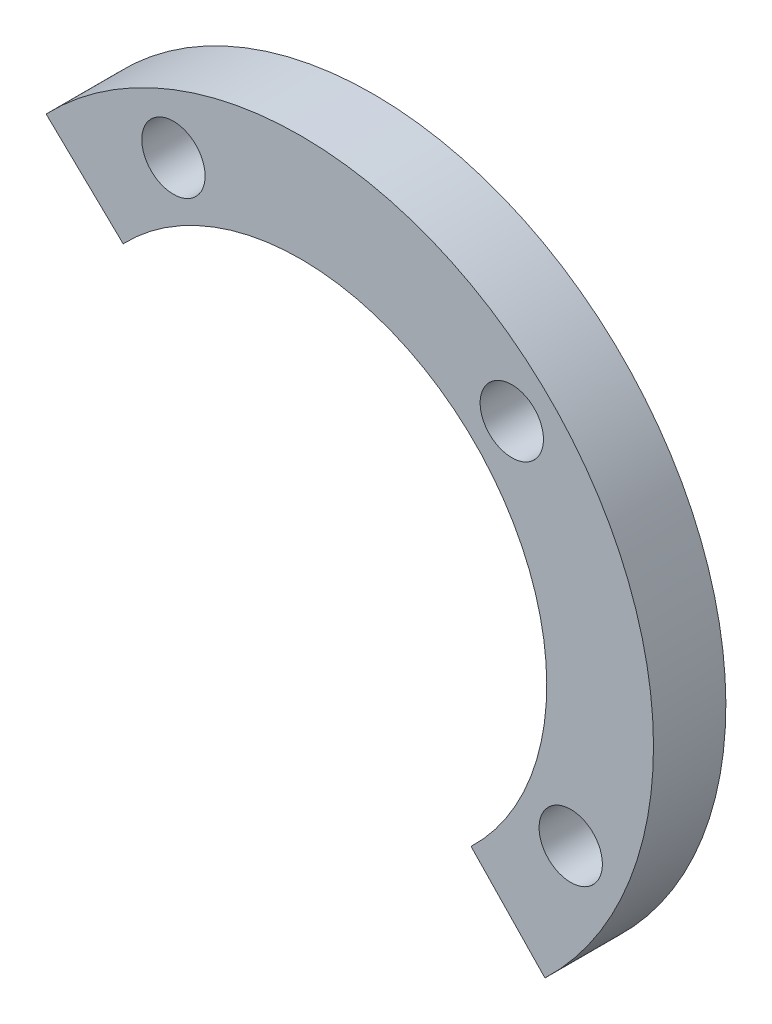
SolidWorks part; units mm, degrees
ref_plane "Front Plane" through (0, 0, 0) normal (0, 0, 1) x (1, 0, 0)
ref_plane "Top Plane" through (0, 0, 0) normal (0, 1, 0) x (1, 0, 0)
ref_plane "Right Plane" through (0, 0, 0) normal (1, 0, 0) x (0, 0, -1)
sketch "Sketch1" plane through (0, 0, 0) normal (0, 0, 1) x (1, 0, 0)
  line L0 (78.5, 50.9288) -> (74.4154, 55.1862)
  line L2 (50.9288, 78.5) -> (55.1862, 74.4154)
  arc A0 (78.5, 50.9288) -> (50.9288, 78.5) centre (65, 65) ccw construction
  arc A1 (78.5, 50.9288) -> (50.9288, 78.5) centre (65, 65) ccw
  circle A2 centre (57.9654, 79.9253) radius 1.75 construction
  circle A3 centre (76.6673, 76.6673) radius 1.75 construction
  circle A4 centre (79.9253, 57.9654) radius 1.75 construction
  circle A5 centre (57.9654, 79.9253) radius 1.75
  circle A6 centre (76.6673, 76.6673) radius 1.75
  circle A7 centre (79.9253, 57.9654) radius 1.75
  circle A8 centre (65, 65) radius 13.6
  circle A9 centre (65, 65) radius 13.5 construction
  dimension "D1" = 0.1
extrude "Boss-Extrude1" add sketch "Sketch1" along normal blind 4 contours A8 L0 A1 L2 A7 A6 A5 region at (76.8003, 53.3862, 0)
